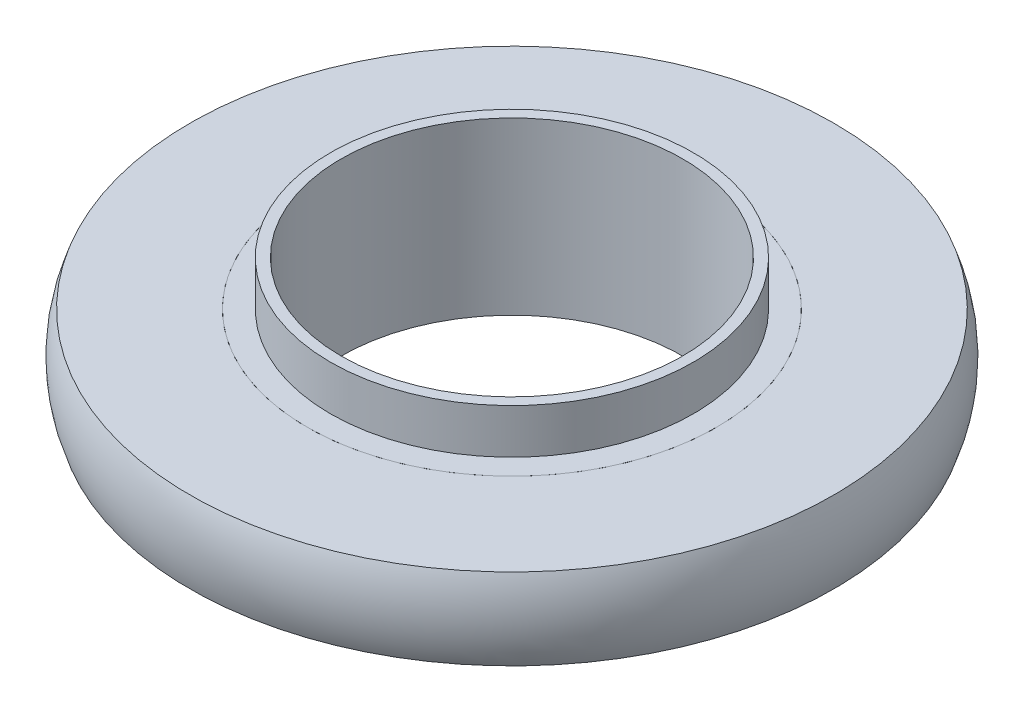
SolidWorks part; units mm, degrees
material "AISI 304"
ref_plane "Front Plane" through (0, 0, 0) normal (0, 0, 1) x (1, 0, 0)
ref_plane "Top Plane" through (0, 0, 0) normal (0, 1, 0) x (1, 0, 0)
ref_plane "Right Plane" through (0, 0, 0) normal (1, 0, 0) x (0, 0, -1)
sketch "Sketch1" plane through (0, 0, 0) normal (0, 0, 1) x (1, 0, 0)
  line L0 (0, 4) -> (0, -4) construction
  line L1 (8, 4) -> (8, -4)
  line L2 (8, -4) -> (8.5, -4)
  line L3 (8.5, -4) -> (8.5, -1.905)
  line L4 (8.5, -1.905) -> (9.5892, -1.905)
  line L5 (8, 4) -> (8.5, 4)
  line L6 (8.5, 4) -> (8.5, 1.905)
  line L7 (8.5, 1.905) -> (9.5892, 1.905)
  arc A0 (9.5892, 1.905) -> (9.5892, -1.905) centre (14.535, 0) ccw
  dimension "D5" = 5.3
  dimension "D1" = 8
  dimension "D2" = 3.81
  dimension "InnerD" = 16
  dimension "LipD" = 17
  dimension "SealD" = 18.47
revolve "Revolve1" add sketch "Sketch1" angle 360 about L0
sketch "Sketch2" plane through (0, 0, 0) normal (0, 0, 1) x (1, 0, 0)
  line L0 (9.5892, 1.905) -> (15.0808, 1.905)
  line L1 (9.5892, -1.905) -> (15.0808, -1.905)
  line L2 (12.335, 1.905) -> (12.335, -1.905) construction
  line L4 (12.335, 0) -> (11.935, 0) construction
  line L5 (0, -4) -> (0, 4) construction
  arc A0 (9.5892, 1.905) -> (9.5892, -1.905) centre (14.535, 0) ccw construction
  arc A1 (9.5892, 1.905) -> (9.5892, -1.905) centre (14.535, 0) ccw
  arc A2 (15.0808, 1.905) -> (15.0808, -1.905) centre (10.135, 0) cw
  circle A3 centre (11.935, 0) radius 2.7 construction
  dimension "D1" = 5.4
  dimension "D2" = 6.2
revolve "Revolve2" add sketch "Sketch2" angle 360 about L5
ref_axis "Axis1" through (0, -4, 0) along (0, 1, 0)
